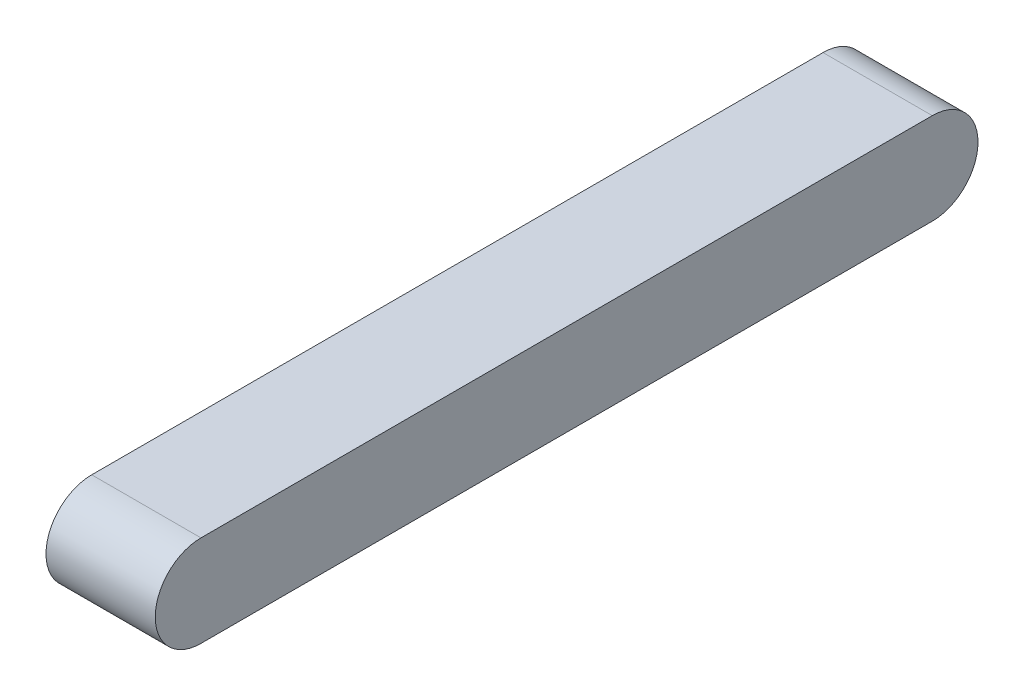
SolidWorks part; units mm, degrees
ref_plane "Płaszczyzna przednia" through (0, 0, 0) normal (0, 0, 1) x (1, 0, 0)
ref_plane "Płaszczyzna górna" through (0, 0, 0) normal (0, 1, 0) x (1, 0, 0)
ref_plane "Płaszczyzna prawa" through (0, 0, 0) normal (1, 0, 0) x (0, 0, -1)
sketch "Szkic1" plane through (0, 0, 0) normal (0, 0, 1) x (1, 0, 0)
  line L1 (-2.39, 2) -> (2.39, 2)
  line L2 (-2.39, 2) -> (-2.39, -2)
  line L3 (-2.39, -2) -> (2.39, -2)
  line L4 (2.39, 2) -> (2.39, -2)
  point P4 (0, -2)
  point P5 (-2.39, 0)
  dimension "D1" = 4
  dimension "D2" = 4.78
extrude "Dodanie-wyciągnięcie1" add sketch "Szkic1" along normal blind 36 contours L3 L4 L1 L2
fillet "Zaokrąglenie1" 2 edges at (0, 2, 36) (0, -2, 36) type full round first side face at (0, 2, 18) second side face at (0, -2, 18) middle face at (0, 0, 36)
fillet "Zaokrąglenie2" 2 edges at (0, 2, 0) (0, -2, 0) type full round first side face at (0, 2, 17) second side face at (0, -2, 17) middle face at (0, 0, 0)
